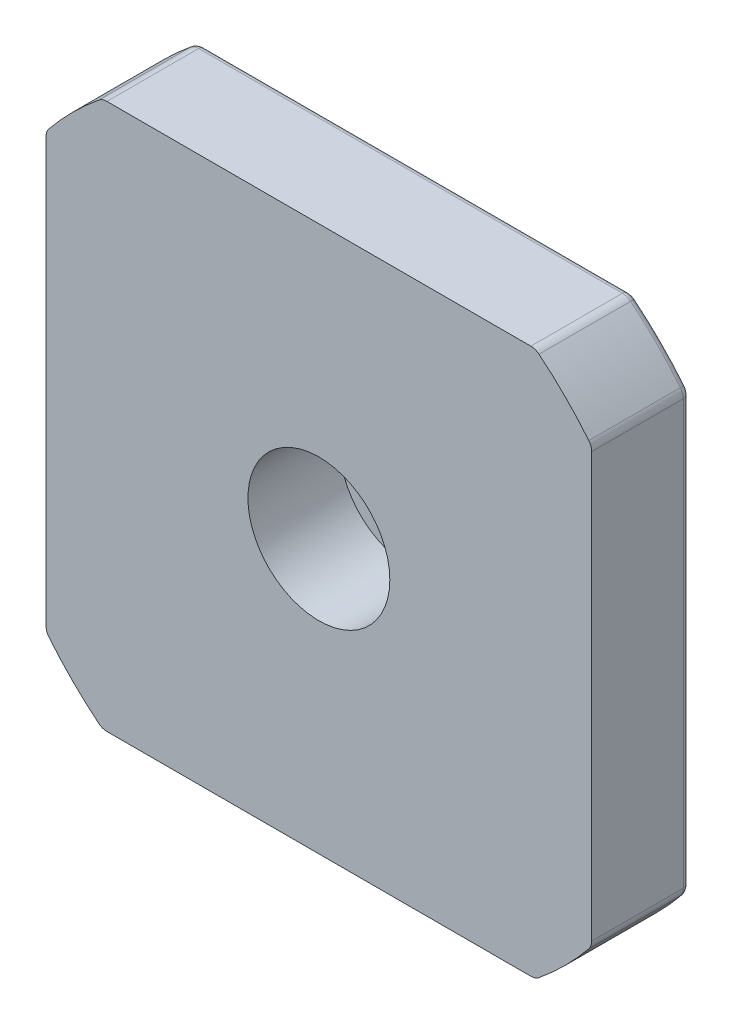
SolidWorks part; units mm, degrees
material "Acero aleado"
ref_plane "Alzado" through (0, 0, 0) normal (0, 0, 1) x (1, 0, 0)
ref_plane "Planta" through (0, 0, 0) normal (0, 1, 0) x (1, 0, 0)
ref_plane "Vista lateral" through (0, 0, 0) normal (1, 0, 0) x (0, 0, -1)
sketch "Croquis1" plane through (0, 0, 0) normal (0, 0, 1) x (1, 0, 0)
  line L0 (21.15, -21.15) -> (-21.15, -21.15)
  line L1 (21.15, 21.15) -> (-21.15, 21.15)
  line L2 (-21.15, 21.15) -> (-21.15, -21.15)
  line L4 (21.15, 21.15) -> (21.15, -21.15)
  line L5 (-21.15, 21.15) -> (21.15, -21.15) construction
  line L6 (-21.15, -21.15) -> (21.15, 21.15) construction
  point P0 (0, 0)
  dimension "D1" = 42.3
  dimension "D2" = 42.3
extrude "Saliente-Extruir1" add sketch "Croquis1" along normal blind 7.6
sketch "Sketch1" plane through (0, 0, 0) normal (0, 0, -1) x (-1, 0, 0)
  circle A0 centre (0, 0) radius 27
  circle A1 centre (0, 0) radius 29.9106
  dimension "D1" = 54
extrude "Cut-Extrude1" cut sketch "Sketch1" against normal through all
sketch "Croquis3" plane through (0, 0, 0) normal (0, 0, -1) x (-1, 0, 0)
  circle A0 centre (0, 0) radius 11
  circle A1 centre (0, 0) radius 8.5
  dimension "D1" = 22
  dimension "D2" = 2.5
extrude "Saliente-Extruir2" add sketch "Croquis3" along normal blind 2
sketch "Croquis4" plane through (0, 0, -2) normal (0, 0, -1) x (-1, 0, 0)
  circle A0 centre (0, 0) radius 4.5
  dimension "D1" = 9
extrude "Cortar-Extruir2" cut sketch "Croquis4" against normal blind 7
sketch "Croquis5" plane through (0, 0, 5) normal (0, 0, -1) x (-1, 0, 0)
  circle A0 centre (0, 0) radius 2.5
  dimension "D1" = 5
extrude "Cortar-Extruir3" cut sketch "Croquis5" against normal blind 7
sketch "Croquis6" plane through (0, 0, 0) normal (0, 0, -1) x (-1, 0, 0)
  circle A0 centre (-15.5, 15.5) radius 1.5
  circle A1 centre (15.5, 15.5) radius 1.5
  circle A2 centre (15.5, -15.5) radius 1.5
  circle A3 centre (-15.5, -15.5) radius 1.5
  point P12 (0, 0)
  dimension "D1" = 3
  dimension "D2" = 15.5
  dimension "D3" = 15.5
  dimension "D5" = 15.5
  dimension "D6" = 15.5
  dimension "D4" = 4
extrude "Cortar-Extruir4" cut sketch "Croquis6" against normal blind 4.5
sketch "Sketch2" plane through (0, 0, 7.6) normal (0, 0, 1) x (1, 0, 0)
  circle A0 centre (0, 0) radius 5.5
  dimension "D1" = 11
extrude "Cut-Extrude2" cut sketch "Sketch2" against normal offset from surface (7.1 mm away) 0.5 up to face at (-4.5, 0, 0)
sketch "Sketch3" plane through (0, 0, 0) normal (0, 0, -1) x (-1, 0, 0)
  circle A0 centre (0, 0) radius 16.5
  circle A1 centre (0, 0) radius 11.5
  circle A2 centre (0, 0) radius 11 construction
  dimension "D1" = 33
  dimension "D2" = 0.5
extrude "Cut-Extrude3" cut sketch "Sketch3" against normal blind 0.1
fillet "Fillet1" radius 1 8 edges at (16.7833, 21.15, 3.8) (21.15, 16.7833, 3.8) (21.15, -16.7833, 3.8) (16.7833, -21.15, 3.8) (-16.7833, -21.15, 3.8) (-21.15, -16.7833, 3.8) (-21.15, 16.7833, 3.8) (-16.7833, 21.15, 3.8)
fillet "Fillet2" radius 0.5 16 edges at (-21.0921, 16.7664, 0) (-21.15, 0, 0) (-21.0921, -16.7664, 0) (-19.0919, -19.0919, 0) (-16.7664, -21.0921, 0) (0, -21.15, 0) (16.7664, -21.0921, 0) (19.0919, -19.0919, 0) (21.0921, -16.7664, 0) (21.15, 0, 0) (21.0921, 16.7664, 0) (19.0919, 19.0919, 0) (16.7664, 21.0921, 0) (0, 21.15, 0) (-16.7664, 21.0921, 0) (-19.0919, 19.0919, 0)
chamfer "Chamfer1" distance 0.5 angle 45 1 edges at (-11, 0, -2)
